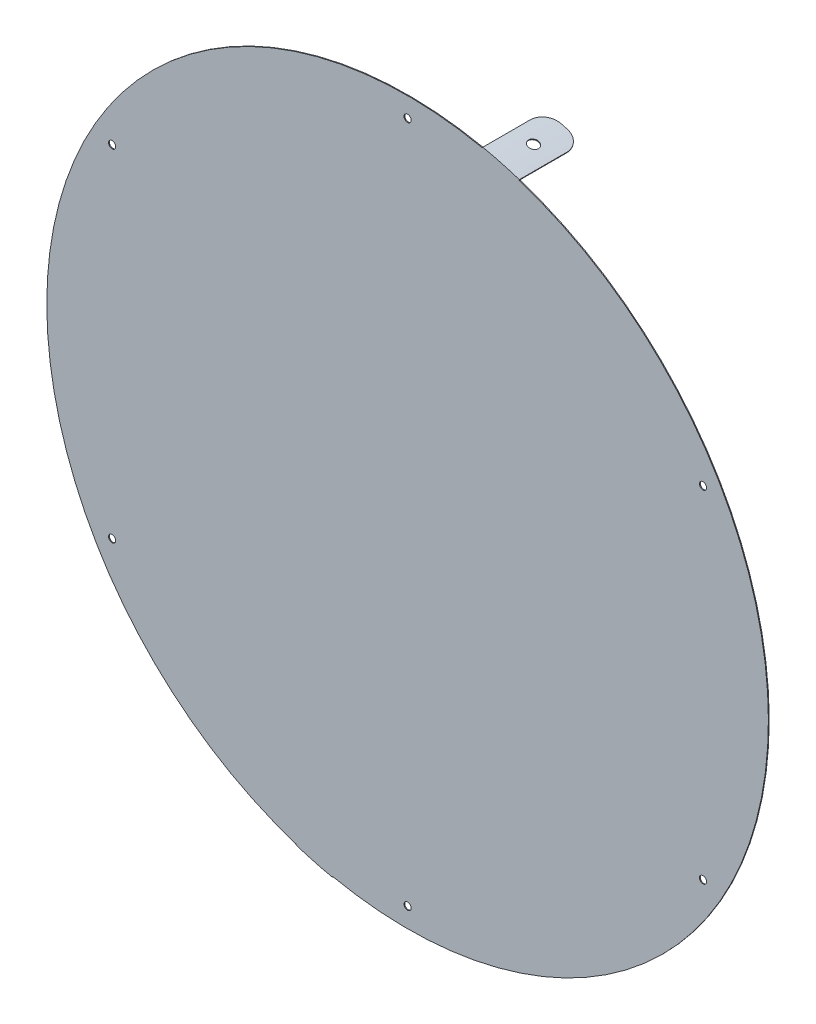
SolidWorks part; units mm, degrees
material "Copper"
ref_plane "Front Plane" through (0, 0, 0) normal (0, 0, 1) x (1, 0, 0)
ref_plane "Top Plane" through (0, 0, 0) normal (0, 1, 0) x (1, 0, 0)
ref_plane "Right Plane" through (0, 0, 0) normal (1, 0, 0) x (0, 0, -1)
sketch "Sketch1" plane through (0, 0, 0) normal (0, 0, 1) x (1, 0, 0)
  circle A0 centre (-20.0737, -8.1031) radius 114.3
  circle A1 centre (-113.6586, 45.9281) radius 1.1303
  circle A2 centre (-20.0737, -8.1031) radius 105
  circle A3 centre (-20.0737, 99.9594) radius 1.1303
  circle A4 centre (73.5112, 45.9281) radius 1.1303
  circle A5 centre (73.5112, -62.1344) radius 1.1303
  circle A6 centre (-20.0737, -116.1656) radius 1.1303
  circle A7 centre (-113.6586, -62.1344) radius 1.1303
  circle A8 centre (-20.0737, -8.1031) radius 108.0625 construction
  dimension "D1" = 210
  dimension "D2" = 228.6
  dimension "D3" = 2.2606
  dimension "D4" = 216.125
extrude "Boss-Extrude1" add sketch "Sketch1" along normal blind 0.254 contours A2 | A0 A7 A6 A5 A4 A3 A2 A1 region at (-131.1408, -8.1031, 0) region at (-20.0737, -8.1031, 0)
sketch "Sketch2" plane through (0, 0, 0.254) normal (0, 0, 1) x (1, 0, 0)
  line L0 (-20.0737, 106.1969) -> (-20.0737, -8.1031) construction
  line L1 (-20.0737, -8.1031) -> (78.913, 49.0469) construction
  line L2 (-20.0737, -8.1031) -> (9.5093, 102.3022) construction
  line L3 (-20.0737, -8.1031) -> (3.7434, 103.9476)
  line L4 (-20.0737, -8.1031) -> (15.3254, 100.8442)
  circle A0 centre (-20.0737, -8.1031) radius 114.554
  circle A1 centre (-20.0737, -8.1031) radius 114.3
  circle A2 centre (-20.0737, -8.1031) radius 114.3
  circle M8 centre (-20.0737, -8.1031) radius 114.3
  dimension "D2" = 60
  dimension "D3" = 15
  dimension "D5" = 3
  dimension "D1" = 0
  dimension "D4" = 0.254
extrude "Boss-Extrude2" add sketch "Sketch2" against normal blind 20 contours L4 A0 L3 M8 region at (9.5287, 102.3744, 0.254)
ref_plane "Plane1" through (9.575, 102.5475, 0.254) normal (0.2588, 0.9659, 0) x (-0.9659, 0.2588, 0)
sketch "Sketch3" plane through (9.575, 102.5475, 0.254) normal (0.2588, 0.9659, 0) x (-0.9659, 0.2588, 0)
  line L0 (0, -20) -> (0, 0) construction
  line L1 (-114.3, -0.254) -> (114.3, -0.254) construction
  line L4 (5.9953, 0) -> (-5.9953, 0)
  line L5 (-5.9953, 0) -> (-5.9953, -20)
  line L6 (-5.9953, -20) -> (5.9953, -20)
  line L7 (5.9953, -20) -> (5.9953, 0)
  line L8 (5.9953, 0) -> (-5.9953, 0)
  line L9 (-5.9953, 0) -> (-5.9953, -15)
  line L10 (-0.9953, -20) -> (0.9953, -20)
  line L11 (5.9953, -15) -> (5.9953, 0)
  line L17 (-5.9953, -15) -> (-5.9953, -20)
  line L18 (-5.9953, -20) -> (5.9953, -20)
  line L19 (5.9953, -20) -> (5.9953, -15)
  arc A0 (5.9953, -15) -> (0.9953, -20) centre (0.9953, -15) cw
  arc A1 (-0.9953, -20) -> (-5.9953, -15) centre (-0.9953, -15) cw
  circle A2 centre (0, -10.254) radius 1.6319
  dimension "D2" = 5
  dimension "D3" = 10
  dimension "D4" = 3.2639
  dimension "D1" = 0
extrude "Cut-Extrude1" cut sketch "Sketch3" against normal through all contours A2 L0 | L0 A2 | L19 A0 L18 | L18 A1 L17 region at (10.2441, 102.3683, -10) region at (8.906, 102.7268, -10) region at (14.2873, 101.2849, -18.6292) region at (4.8628, 103.8102, -18.6292)
ref_axis "Axis1" through (-20.0737, -8.1031, 0.254) along (0, 0, -1)
pattern_circular "CirPattern1" count 2 over 360 about axis through (-20.0737, -8.1031, 0.254) along (0, 0, -1) of "Boss-Extrude2", "Cut-Extrude1"
